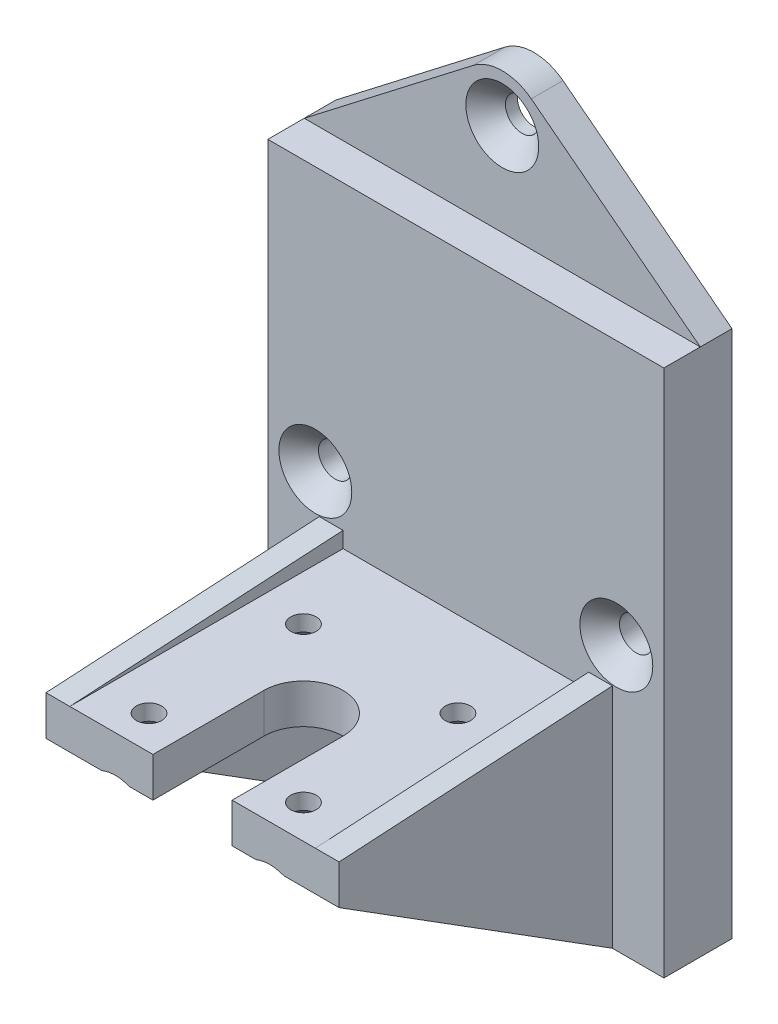
SolidWorks part; units mm, degrees
other "carriage coupler plate"
material "PET"
ref_plane "Front" through (0, 0, 0) normal (0, 0, 1) x (1, 0, 0)
ref_plane "Top" through (0, 0, 0) normal (0, 1, 0) x (1, 0, 0)
ref_plane "Right" through (0, 0, 0) normal (1, 0, 0) x (0, 0, -1)
sketch "Sketch1" plane through (0, 0, 0) normal (0, 0, 1) x (1, 0, 0)
  line L0 (0, 0) -> (0, 30) construction
  line L1 (0, 0) -> (25.9808, -15) construction
  line L2 (0, 0) -> (-25.9808, -15) construction
  dimension "D1" = 120
  dimension "D2" = 120
  dimension "D3" = 30
ref_plane "Plane1" through (0, 30, 0) normal (0, 1, 0) x (1, 0, 0)
sketch "Sketch2" plane through (0, 30, 0) normal (0, 1, 0) x (1, 0, 0)
  line L0 (-4.4589, 0) -> (0, -4.0148) construction
  line L1 (0, 0) -> (-25.9808, 0) construction
  line L2 (0, 0) -> (0, -4.0148) construction
  line L3 (-4.4589, 0) -> (0, 0) construction
  line L4 (0, -5.3962) -> (0, -4.0148) construction
  line L5 (0, -5.3962) -> (-4.4589, 0) construction
  line L7 (-4, -4.0148) -> (4, -4.0148) construction
  line L8 (3.9519, -3.3962) -> (-3.9519, -3.3962) construction
  line L9 (0, -0.3962) -> (0, -3.3962) construction
  line L10 (0, -4.0148) -> (0, -7.3926) construction
  circle A0 centre (-4.4589, 0) radius 2
  circle A1 centre (4.4589, 0) radius 2
  circle A2 centre (0, -4.0148) radius 4
  circle A3 centre (0, -5.3962) radius 5 construction
  circle A4 centre (0, -7.3926) radius 1.5
  dimension "D1" = 4
  dimension "D2" = 8
  dimension "D4" = 10
  dimension "D9" = 3
  dimension "D6" = 7.3926
  dimension "D8" = 8.9177
  dimension "D3" = 42
  dimension "D5" = 50.433
  dimension "D7" = 3.3962
  dimension "D10" = 0.6186
sketch "Sketch3" plane through (0, 0, 0) normal (0, 0, 1) x (1, 0, 0)
  line L0 (0, 30) -> (0, 35) construction
  line L2 (0, 35) -> (0, 39) construction
  line L3 (-25, 39) -> (25, 39)
  line L4 (25, 39) -> (25, -27.6916)
  line L6 (0, 0) -> (0, 30) construction
  line L8 (-25, 39) -> (-25, -27.6916)
  line L9 (4.4589, 30) -> (4.4589, 39) construction
  line L11 (25, -27.6916) -> (-25, -27.6916)
  line L15 (4.4589, 30) -> (0, 30) construction
  line L16 (4.4589, 30) -> (9.4589, 30) construction
  dimension "D1" = 5
  dimension "D2" = 4
  dimension "D3" = 25
  dimension "D4" = 25
  dimension "D5" = 5
  dimension "D6" = 9.4589
  dimension "D7" = 27.6916
  dimension "D8" = 9
extrude "Boss-Extrude1" add sketch "Sketch3" along normal blind 2.6 and the other way blind 6
sketch "Sketch7" plane through (0, 0, -6) normal (0, 0, -1) x (-1, 0, 0)
  line L0 (-25, 39) -> (-3.6637, 55.4515)
  line L1 (25, 39) -> (3.6637, 55.4515)
  line L2 (0, 0) -> (0, 50.7) construction
  line L3 (-25, 39) -> (25, 39) construction
  line L4 (-25, 39) -> (25, 39)
  arc A0 (3.6637, 55.4515) -> (-3.6637, 55.4515) centre (0, 50.7) ccw
  point P1 (0, 0)
  point P12 (0, 0)
  point P13 (0, 10.8615)
  dimension "D1" = 12
  dimension "D2" = 11.7
extrude "Boss-Extrude2" add sketch "Sketch7" against normal blind 4
sketch "Sketch8" plane through (0, 0, 2.6) normal (0, 0, 1) x (1, 0, 0)
  line L0 (0, 0) -> (0, 50.7) construction
  line L1 (-19, 5.7) -> (19, 5.7) construction
  circle A0 centre (-19, 5.7) radius 2.1
  circle A1 centre (19, 5.7) radius 2.1
  circle A2 centre (0, 50.7) radius 2.1
  arc A3 (3.6637, 55.4515) -> (-3.6637, 55.4515) centre (0, 50.7) ccw construction
  point P10 (0, 5.7)
  dimension "D1" = 4.2
  dimension "D2" = 4.2
  dimension "D3" = 4.2
  dimension "D4" = 45
  dimension "D5" = 38
extrude "Cut-Extrude4" cut sketch "Sketch8" against normal through all
chamfer "Chamfer1" distance 2.5 angle 45 3 edges at (-16.9, 5.7, 2.6) (21.1, 5.7, 2.6) (-2.1, 50.7, -2)
sketch "Sketch9" plane through (0, 0, 2.6) normal (0, 0, 1) x (1, 0, 0)
  line L0 (25, 39) -> (-25, 39) construction
  line L1 (-18.5, -1) -> (18.5, -1)
  line L2 (-18.5, -1) -> (-18.5, -6)
  line L3 (-18.5, -6) -> (18.5, -6)
  line L4 (18.5, -1) -> (18.5, -6)
  dimension "D1" = 40
  dimension "D2" = 5
  dimension "D3" = 18.5
  dimension "D4" = 37
extrude "Boss-Extrude3" add sketch "Sketch9" along normal blind 34.5
sketch "Sketch10" plane through (0, -1, 0) normal (0, 1, 0) x (1, 0, 0)
  line L0 (0, -37.1) -> (0, -2.6) construction
  line L1 (18.5, -37.1) -> (-18.5, -37.1) construction
  line L2 (18.5, -2.6) -> (-18.5, -2.6) construction
  line L3 (-5, -23.1) -> (-5, -37.1)
  line L4 (-9.75, -13.35) -> (9.75, -13.35) construction
  line L5 (-9.75, -13.35) -> (-9.75, -32.85) construction
  line L6 (-9.75, -32.85) -> (9.75, -32.85) construction
  line L7 (9.75, -13.35) -> (9.75, -32.85) construction
  line L8 (-9.75, -13.35) -> (9.75, -32.85) construction
  line L9 (-9.75, -32.85) -> (9.75, -13.35) construction
  line L10 (5, -23.1) -> (5, -37.1)
  line L11 (5, -37.1) -> (-5, -37.1)
  circle A0 centre (9.75, -13.35) radius 1.6
  circle A1 centre (9.75, -32.85) radius 1.6
  circle A2 centre (-9.75, -32.85) radius 1.6
  circle A3 centre (-9.75, -13.35) radius 1.6
  arc A4 (5, -23.1) -> (-5, -23.1) centre (0, -23.1) ccw
  point P6 (0, -23.1)
  dimension "D4" = 3.2
  dimension "D5" = 3.2
  dimension "D6" = 3.2
  dimension "D7" = 3.2
  dimension "D8" = 10
  dimension "D1" = 14
  dimension "D2" = 19.5
  dimension "D3" = 19.5
extrude "Cut-Extrude5" cut sketch "Sketch10" against normal through all
sketch "Sketch11" plane through (-18.5, 0, 0) normal (-1, 0, 0) x (0, 0, 1)
  line L0 (2.6, -1) -> (2.6, 1)
  line L1 (2.6, 1) -> (37.1, -1)
  line L2 (37.1, -1) -> (2.6, -1)
  line L3 (2.6, -6) -> (2.6, -27.6916)
  line L4 (2.6, -27.6916) -> (37.1, -6)
  line L5 (37.1, -6) -> (2.6, -6)
  dimension "D1" = 2
extrude "Boss-Extrude4" add sketch "Sketch11" against normal blind 3
mirror "Mirror1" about plane through (0, 0, 0) normal (1, 0, 0) of "Boss-Extrude4"
chamfer "Chamfer2" distance 3 angle 45 4 edges at (8.15, -6, 32.85) (8.15, -6, 13.35) (-11.35, -6, 32.85) (-11.35, -6, 13.35)
